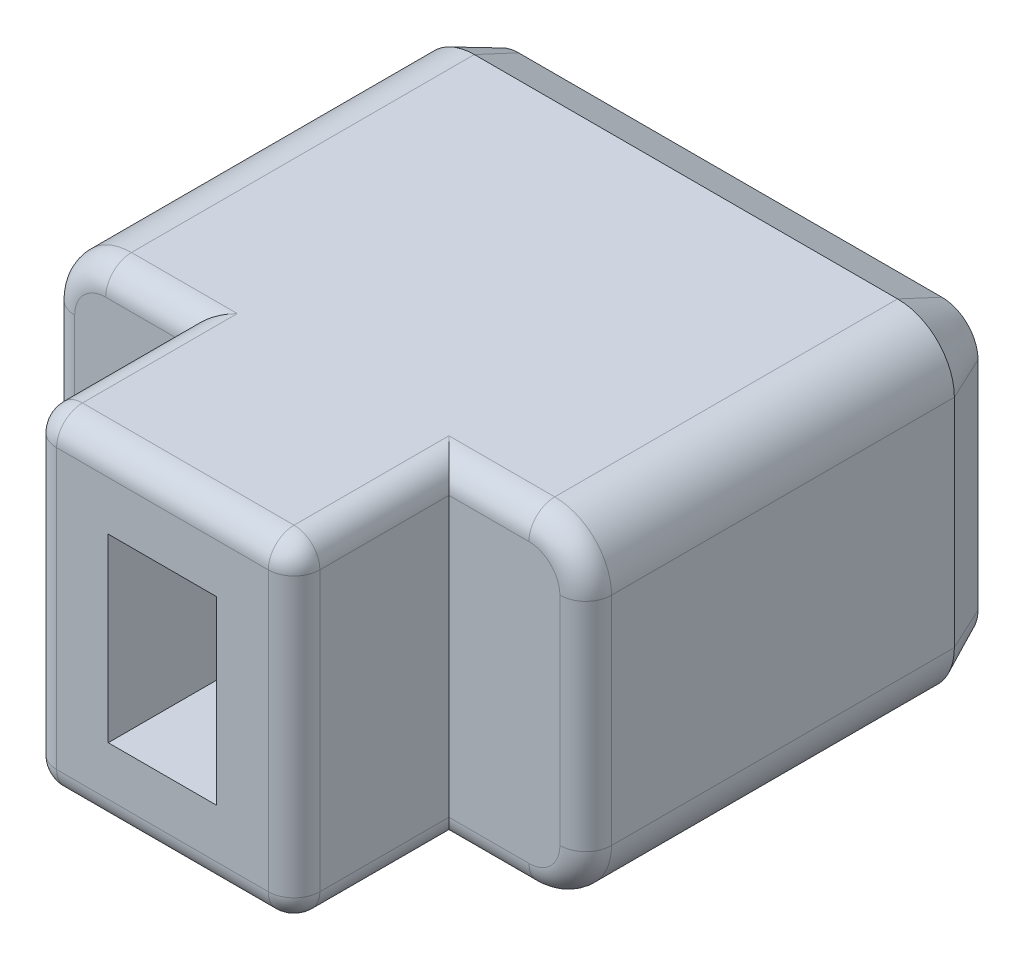
SolidWorks part; units mm, degrees
ref_plane "Plan de face" through (0, 0, 0) normal (0, 0, 1) x (1, 0, 0)
ref_plane "Plan de dessus" through (0, 0, 0) normal (0, 1, 0) x (1, 0, 0)
ref_plane "Plan de droite" through (0, 0, 0) normal (1, 0, 0) x (0, 0, -1)
sketch "Esquisse2" plane through (0, 0, 0) normal (0, 0, 1) x (1, 0, 0)
  line L1 (1.1, 0) -> (9.3, 0)
  line L2 (0, 1.1) -> (0, 5.3)
  line L3 (1.1, 6.4) -> (9.3, 6.4)
  line L4 (10.4, 1.1) -> (10.4, 5.3)
  arc A0 (9.3, 6.4) -> (10.4, 5.3) centre (9.3, 5.3) cw
  arc A1 (9.3, 0) -> (10.4, 1.1) centre (9.3, 1.1) ccw
  arc A2 (1.1, 0) -> (0, 1.1) centre (1.1, 1.1) cw
  arc A3 (0, 5.3) -> (1.1, 6.4) centre (1.1, 5.3) cw
  point P7 (10.4, 6.4)
  point P12 (0, 0)
  point P15 (0, 6.4)
  dimension "D3" = 1.1
  dimension "D1" = 10.4
  dimension "D2" = 6.4
extrude "Boss.-Extru.1" add sketch "Esquisse2" along normal blind 11
sketch "Esquisse3" plane through (0, 0, 11) normal (0, 0, 1) x (1, 0, 0)
  line L0 (0, 5.3) -> (0, 1.1) construction
  line L1 (4.15, 4.95) -> (6.25, 4.95)
  line L2 (4.15, 4.95) -> (4.15, 1.45)
  line L3 (4.15, 1.45) -> (6.25, 1.45)
  line L4 (6.25, 4.95) -> (6.25, 1.45)
  line L5 (10.4, 1.1) -> (10.4, 5.3) construction
  line L6 (9.3, 6.4) -> (1.1, 6.4) construction
  line L7 (1.1, 0) -> (9.3, 0) construction
  dimension "D1" = 2.1
  dimension "D2" = 3.5
  dimension "D3" = 4.15
  dimension "D4" = 4.15
  dimension "D5" = 1.45
  dimension "D6" = 1.45
extrude "Enlèv. mat.-Extru.1" cut sketch "Esquisse3" against normal blind 3
sketch "Esquisse4" plane through (0, 0, 11) normal (0, 0, 1) x (1, 0, 0)
  line L0 (2.65, 6.4) -> (2.65, 0)
  line L1 (9.3, 6.4) -> (1.1, 6.4) construction
  line L2 (1.1, 0) -> (9.3, 0) construction
  line L3 (2.65, 0) -> (7.75, 0)
  line L4 (7.75, 0) -> (7.75, 6.4)
  line L5 (7.75, 6.4) -> (2.65, 6.4)
  line L6 (4.15, 4.95) -> (4.15, 1.45) construction
  line L7 (6.25, 1.45) -> (6.25, 4.95) construction
  dimension "D1" = 1.5
  dimension "D2" = 1.5
extrude "Enlèv. mat.-Extru.2" cut sketch "Esquisse4" against normal blind 3 flip side to cut
fillet "Congé1" radius 0.5 18 edges at (8.525, 0, 8) (10.0778, 0.3222, 8) (10.4, 3.2, 8) (10.0778, 6.0778, 8) (1.875, 6.4, 8) (0.3222, 6.0778, 8) (1.875, 0, 8) (0.3222, 0.3222, 8) (7.75, 6.4, 9.5) (2.65, 6.4, 9.5) (7.75, 0, 9.5) (2.65, 0, 9.5) (2.65, 3.2, 11) (5.2, 6.4, 11) (7.75, 3.2, 11) (5.2, 0, 11) (8.525, 6.4, 8) (0, 3.2, 8)
chamfer "Chanfrein1" distance 0.4 angle 65 8 edges at (5.2, 0, 0) (10.0778, 0.3222, 0) (0.3222, 0.3222, 0) (10.4, 3.2, 0) (0, 3.2, 0) (10.0778, 6.0778, 0) (0.3222, 6.0778, 0) (5.2, 6.4, 0) first distance on face at (5.2, 3.2, 0)
sketch "Esquisse5" plane through (0, 0, 0) normal (0, 0, -1) x (-1, 0, 0)
  line L0 (-0.4, 5.3) -> (-10, 5.3) construction
  arc A0 (-9.3, 6) -> (-10, 5.3) centre (-9.3, 5.3) ccw construction
  text T0 "5" font "Century Gothic" height 4
extrude "Enlèv. mat.-Extru.3" cut sketch "Esquisse5" against normal blind 0.3
extrude "Boss.-Extru.2" add sketch "Esquisse5<2>" along normal blind 0.3 separate body
sketch "Esquisse5<2>" plane through (0, 0, 0) normal (0, 0, -1) x (-1, 0, 0) same geometry as "Esquisse5"
